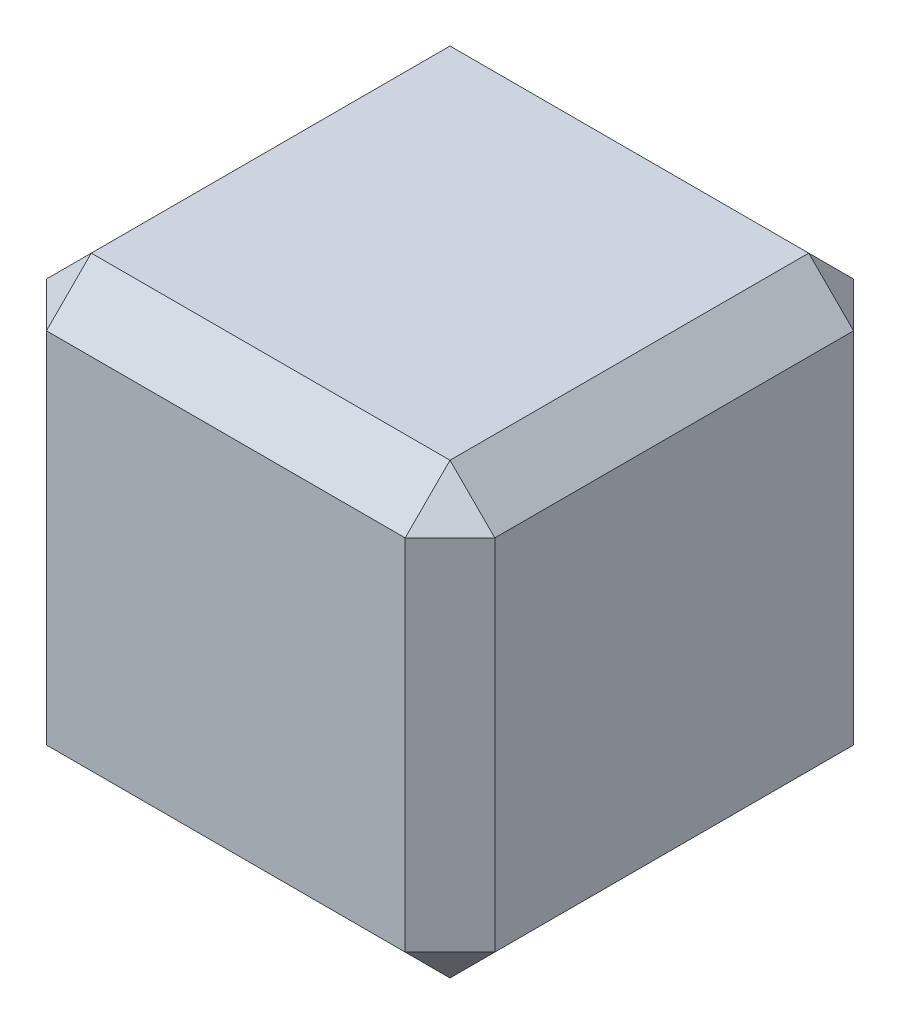
SolidWorks part; units mm, degrees
ref_plane "前视基准面" through (0, 0, 0) normal (0, 0, 1) x (1, 0, 0)
ref_plane "上视基准面" through (0, 0, 0) normal (0, 1, 0) x (1, 0, 0)
ref_plane "右视基准面" through (0, 0, 0) normal (1, 0, 0) x (0, 0, -1)
other "Configuration Table"
sketch "草图1" plane through (0, 0, 0) normal (1, 0, 0) x (0, 0, -1)
  line L1 (-39.8978, 88.1395) -> (80.1022, 88.1395)
  line L2 (-39.8978, 88.1395) -> (-39.8978, -31.8605)
  line L3 (-39.8978, -31.8605) -> (80.1022, -31.8605)
  line L4 (80.1022, 88.1395) -> (80.1022, -31.8605)
extrude "凸台-拉伸1" add sketch "草图1" along normal blind 120
chamfer "倒角1" distance 12 angle 45 12 edges at (60, 88.1395, 39.8978) (120, 28.1395, 39.8978) (60, -31.8605, 39.8978) (0, 28.1395, 39.8978) (60, -31.8605, -80.1022) (120, 88.1395, -20.1022) (120, -31.8605, -20.1022) (120, 28.1395, -80.1022) (60, 88.1395, -80.1022) (0, 88.1395, -20.1022) (0, 28.1395, -80.1022) (0, -31.8605, -20.1022)
ref_point "点4"
ref_point "点6"
sketch "草图2" plane through (120, 0, 0) normal (1, 0, 0) x (0, 0, -1)
  line L0 (20.1022, 28.1395) -> (-11.9526, 28.1395)
ref_axis "基准轴1" through (120, 28.1395, -20.1022) along (0, 0, 1)
ref_axis "基准轴2" through (120, 28.1395, -20.1022) along (1, 0, 0)
